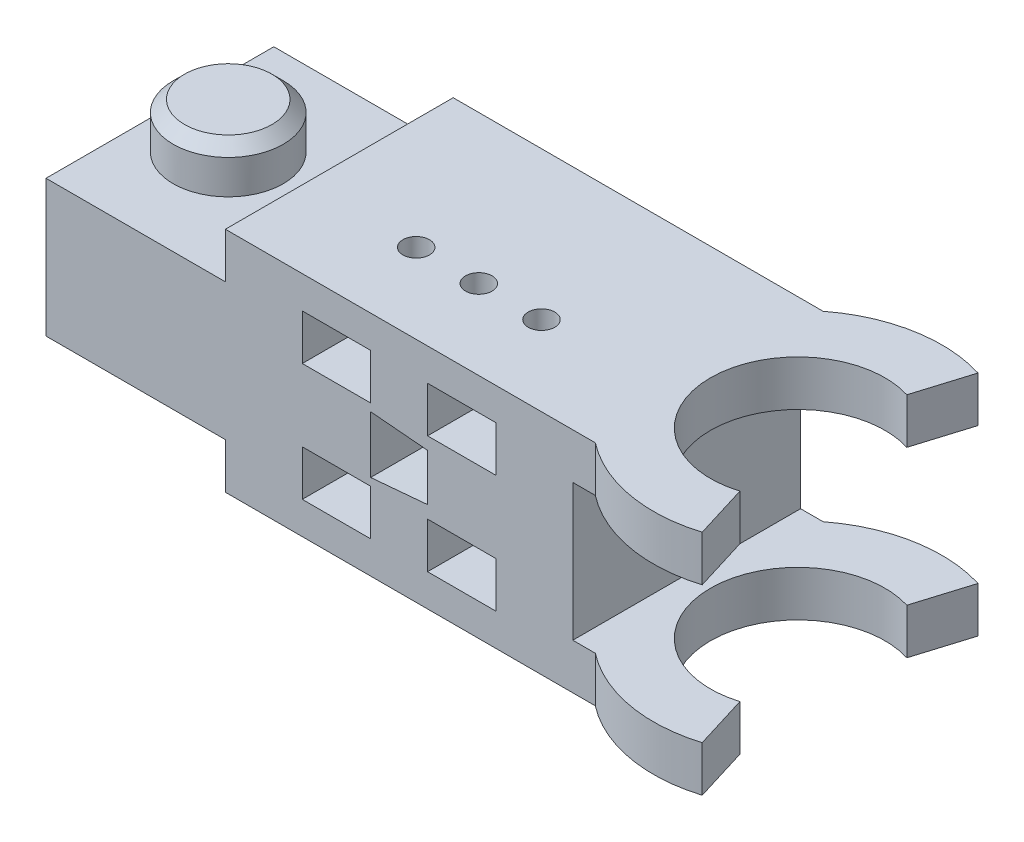
SolidWorks part; units mm, degrees
ref_plane "Front Plane" through (0, 0, 0) normal (0, 0, 1) x (1, 0, 0)
ref_plane "Top Plane" through (0, 0, 0) normal (0, 1, 0) x (1, 0, 0)
ref_plane "Right Plane" through (0, 0, 0) normal (1, 0, 0) x (0, 0, -1)
sketch "Sketch1" plane through (0, 0, 0) normal (0, 0, 1) x (1, 0, 0)
  line L0 (0, 0) -> (-19.5, 0) construction
  line L5 (-19.5, 0) -> (-30.5, 0) construction
  line L6 (-30.5, 0) -> (-50, 0) construction
  line L7 (-50, -6) -> (-42.5, -6) construction
  line L8 (-50, -10) -> (0, -10) construction
  line L9 (-50, -10) -> (-50, 10) construction
  line L10 (-50, 10) -> (0, 10) construction
  line L11 (0, -10) -> (0, 10) construction
  line L12 (-50, -10) -> (0, 10) construction
  line L13 (-50, 10) -> (0, -10) construction
  line L14 (-40.25, -10) -> (-40.25, -6)
  line L15 (-40.25, -6) -> (-50, -6)
  line L16 (-40.25, 10) -> (-40.25, 6)
  line L17 (-40.25, 6) -> (-50, 6)
  line L18 (-50, 6) -> (-56, 6)
  line L19 (-56, 6) -> (-56, -6)
  line L20 (-56, -6) -> (-50, -6)
  line L21 (-40.25, 10) -> (0, 10) construction
  line L22 (-40.25, -10) -> (0, -10)
  line L23 (0, 10) -> (2.25, 10)
  line L24 (2.25, 10) -> (2.25, 6)
  line L25 (2.25, 6) -> (0, 6)
  line L26 (0, -10) -> (2.25, -10)
  line L27 (2.25, -10) -> (2.25, -6)
  line L28 (2.25, -6) -> (0, -6)
  line L29 (0, 6) -> (0, -6) construction
  line L30 (0, 6) -> (-9.75, 6)
  line L31 (-9.75, 6) -> (-9.75, -6)
  line L32 (-9.75, -6) -> (0, -6)
  line L33 (-7.5, 0) -> (0, 0) construction
  line L34 (-7.5, 0) -> (-9.75, 0) construction
  line L35 (-40.25, 10) -> (0, 10)
  line L36 (0, 0) -> (2.25, 0) construction
  line L37 (2.25, 0) -> (2.25, 6) construction
  line L38 (-42.5, -6) -> (-40.25, -6) construction
  point P2 (-25, 0)
  dimension "D2" = 19.5
  dimension "D3" = 11
  dimension "D4" = 19.5
  dimension "D6" = 20
  dimension "D7" = 4
  dimension "D8" = 4
  dimension "D1" = 7.5
  dimension "D9" = 2.25
  dimension "D10" = 6
  dimension "D5" = 7.5
  dimension "D11" = 2.25
  dimension "D12" = 2.25
extrude "Boss-Extrude1" add sketch "Sketch1" along normal blind 20
sketch "Sketch2" plane through (0, -6, 0) normal (0, -1, 0) x (1, 0, 0)
  line L0 (-50, 0) -> (0, 0) construction
  line L1 (-50, 0) -> (0, 0) construction
  line L2 (-50, 0) -> (-50, 20) construction
  line L3 (-56, 20) -> (-40.25, 20) construction
  circle A0 centre (-50, 10) radius 4.835
  dimension "D1" = 9.67
extrude "Boss-Extrude2" add sketch "Sketch2" along normal blind 4
sketch "Sketch3" plane through (0, -10, 0) normal (0, -1, 0) x (1, 0, 0)
  line L0 (0, 0) -> (0, 20) construction
  line L1 (-40.25, 20) -> (2.25, 20) construction
  circle A0 centre (0, 10) radius 7.665
  dimension "D1" = 15.33
extrude "Cut-Extrude1" cut sketch "Sketch3" against normal up to surface (20 mm away) up to face at (-19, 10, 10)
mirror "Mirror1" about plane through (0, 0, 0) normal (0, 1, 0) of "Boss-Extrude2"
sketch "Sketch4" plane through (0, 0, 20) normal (0, 0, 1) x (1, 0, 0)
  line L0 (0, -10) -> (0, 10) construction
  line L1 (0, -10) -> (0, 10) construction
  line L2 (0, 0) -> (-25, 0) construction
  line L3 (-19.5, 0) -> (-30.5, 0) construction
  line L4 (-27.5, 2.5) -> (-22.5, 2.0626)
  line L5 (-27.5, -2.5) -> (-22.5, -2.5) construction
  line L6 (-27.5, -2.5) -> (-27.5, 2.5)
  line L7 (-27.5, 2.5) -> (-22.5, 2.5) construction
  line L8 (-22.5, -2.5) -> (-22.5, 2.5) construction
  line L9 (-27.5, -2.5) -> (-22.5, 2.5) construction
  line L10 (-27.5, 2.5) -> (-22.5, -2.5) construction
  line L11 (-27.5, -2.5) -> (-22.5, -2.0626)
  line L12 (-22.5, 2.0626) -> (-22.5, -2.0626)
  dimension "D1" = 5
  dimension "D2" = 5
  dimension "D3" = 25
  dimension "D4" = 5
  dimension "D5" = 5
extrude "Cut-Extrude2" cut sketch "Sketch4" against normal blind 10
sketch "Sketch5" plane through (0, 0, 20) normal (0, 0, 1) x (1, 0, 0)
  line L0 (-30.5, 0) -> (-50, 0) construction
  line L1 (-19.5, 0) -> (-30.5, 0) construction
  line L2 (0, 0) -> (-19.5, 0) construction
  line L3 (-30.5, 0) -> (-50, 0) construction
  line L4 (-19.5, 0) -> (-30.5, 0) construction
  line L5 (0, 0) -> (-19.5, 0) construction
  line L6 (-30.5, -5.165) -> (-30.5, 5.165) construction
  line L7 (-19.5, -5.165) -> (-19.5, 5.165) construction
  line L9 (-33.5, 7.165) -> (-27.5, 7.165)
  line L10 (-33.5, 7.165) -> (-33.5, 3.165)
  line L11 (-33.5, 3.165) -> (-27.5, 3.165)
  line L12 (-27.5, 7.165) -> (-27.5, 3.165)
  line L13 (-33.5, 7.165) -> (-27.5, 3.165) construction
  line L14 (-33.5, 3.165) -> (-27.5, 7.165) construction
  line L15 (-22.5, 7.165) -> (-16.5, 7.165)
  line L16 (-22.5, 7.165) -> (-22.5, 3.165)
  line L17 (-22.5, 3.165) -> (-16.5, 3.165)
  line L18 (-16.5, 7.165) -> (-16.5, 3.165)
  line L19 (-22.5, 7.165) -> (-16.5, 3.165) construction
  line L20 (-22.5, 3.165) -> (-16.5, 7.165) construction
  line L21 (-22.5, -7.165) -> (-16.5, -7.165)
  line L22 (-22.5, -7.165) -> (-22.5, -3.165)
  line L23 (-22.5, -3.165) -> (-16.5, -3.165)
  line L24 (-16.5, -7.165) -> (-16.5, -3.165)
  line L25 (-22.5, -7.165) -> (-16.5, -3.165) construction
  line L26 (-22.5, -3.165) -> (-16.5, -7.165) construction
  line L27 (-33.5, -7.165) -> (-27.5, -7.165)
  line L28 (-33.5, -7.165) -> (-33.5, -3.165)
  line L29 (-33.5, -3.165) -> (-27.5, -3.165)
  line L30 (-27.5, -7.165) -> (-27.5, -3.165)
  line L31 (-33.5, -7.165) -> (-27.5, -3.165) construction
  line L32 (-33.5, -3.165) -> (-27.5, -7.165) construction
  point P7 (-30.5, 0)
  point P10 (-19.5, 0)
  dimension "D2" = 6
  dimension "D3" = 6.33
extrude "Cut-Extrude3" cut sketch "Sketch5" against normal blind 10
sketch "Sketch6" plane through (0, -10, 0) normal (0, -1, 0) x (1, 0, 0)
  line L0 (-22.5, 10) -> (-16.5, 10) construction
  line L1 (-27.5, 10) -> (-22.5, 10) construction
  line L2 (-33.5, 10) -> (-27.5, 10) construction
  line L3 (-22.5, 10) -> (-16.5, 10) construction
  line L4 (-27.5, 10) -> (-22.5, 10) construction
  line L5 (-33.5, 10) -> (-27.5, 10) construction
  line L6 (-30.5, 10) -> (-30.5, 13) construction
  line L7 (-25, 10) -> (-25, 13) construction
  line L8 (-19.5, 10) -> (-19.5, 13) construction
  circle A0 centre (-30.5, 13) radius 1.165
  circle A1 centre (-25, 13) radius 1.165
  circle A2 centre (-19.5, 13) radius 1.165
  dimension "D2" = 2.33
  dimension "D1" = 3
extrude "Cut-Extrude4" cut sketch "Sketch6" against normal up to surface (20 mm away) up to face at (-13.5692, 10, 10)
sketch "Sketch10" plane through (0, -10, 0) normal (0, -1, 0) x (1, 0, 0)
  line L0 (2.25, 17.3273) -> (3.7177, 22.1071)
  line L1 (3.7177, -2.1071) -> (2.25, 2.6727)
  arc A0 (2.25, 17.3273) -> (2.25, 2.6727) centre (0, 10) ccw construction
  arc A1 (2.25, 17.3273) -> (2.25, 2.6727) centre (0, 10) ccw
  arc A2 (3.7177, 22.1071) -> (3.7177, -2.1071) centre (0, 10) ccw
  dimension "D1" = 5
extrude "Boss-Extrude4" add sketch "Sketch10" against normal up to surface (4 mm away) up to face at (-3.4025, -6, 10)
sketch "Sketch11" plane through (0, 10, 0) normal (0, 1, 0) x (1, 0, 0)
  line L5 (-9.75, -20) -> (-7.7719, -20)
  line L6 (3.7177, -22.1071) -> (2.25, -17.3273)
  line L8 (-7.7719, 0) -> (-9.75, 0)
  line L9 (-9.75, 0) -> (-9.75, -20)
  line L10 (-9.75, -20) -> (-7.7719, -20)
  line L13 (-7.7719, 0) -> (-9.75, 0)
  line L14 (-9.75, 0) -> (-9.75, -20)
  line L15 (3.7177, -22.1071) -> (2.25, -17.3273)
  line L17 (2.25, -2.6727) -> (3.7177, 2.1071)
  line L18 (2.25, -2.6727) -> (3.7177, 2.1071)
  arc A3 (-7.7719, -20) -> (3.7177, -22.1071) centre (0, -10) ccw
  arc A4 (2.25, -2.6727) -> (2.25, -17.3273) centre (0, -10) ccw
  arc A5 (-7.7719, -20) -> (3.7177, -22.1071) centre (0, -10) ccw
  arc A7 (2.25, -2.6727) -> (2.25, -17.3273) centre (0, -10) ccw
  arc A9 (3.7177, 2.1071) -> (-7.7719, 0) centre (0, -10) ccw
  arc A10 (3.7177, 2.1071) -> (-7.7719, 0) centre (0, -10) ccw
  dimension "D1" = 0
extrude "Boss-Extrude5" add sketch "Sketch11" against normal up to surface (4 mm away) up to face at (-3.4025, 6, 10)
chamfer "Chamfer1" distance 3 angle 45 3 edges at (-29.335, -10, 13) (-23.835, -10, 13) (-18.335, -10, 13)
chamfer "Chamfer2" distance 1 angle 45 1 edges at (-50, -10, 5.165)
chamfer "Chamfer3" distance 1 angle 45 1 edges at (-50, 10, 5.165)
sketch "Sketch14" plane through (0, 0, -2.75) normal (0, 0, -1) x (-1, 0, 0)
  line L12 (56, -3) -> (56, 3)
  line L13 (53, 6) -> (40.25, 6)
  line L14 (40.25, 6) -> (40.25, 7)
  line L15 (37.25, 10) -> (-3.7177, 10)
  line L16 (-3.7177, 10) -> (-3.7177, 6)
  line L17 (-3.7177, 6) -> (9.75, 6)
  line L18 (9.75, 6) -> (9.75, -6)
  line L19 (9.75, -6) -> (-3.7177, -6)
  line L20 (-3.7177, -6) -> (-3.7177, -10)
  line L21 (-3.7177, -10) -> (37.25, -10)
  line L22 (40.25, -7) -> (40.25, -6)
  line L23 (40.25, -6) -> (53, -6)
  line L24 (56, -3) -> (56, 3)
  line L25 (53, 6) -> (40.25, 6)
  line L26 (40.25, 6) -> (40.25, 7)
  line L27 (37.25, 10) -> (-3.7177, 10)
  line L28 (-3.7177, 10) -> (-3.7177, 6)
  line L29 (-3.7177, 6) -> (9.75, 6)
  line L30 (9.75, 6) -> (9.75, -6)
  line L31 (9.75, -6) -> (-3.7177, -6)
  line L32 (-3.7177, -6) -> (-3.7177, -10)
  line L33 (-3.7177, -10) -> (37.25, -10)
  line L34 (40.25, -7) -> (40.25, -6)
  line L35 (40.25, -6) -> (53, -6)
  arc A4 (53, -6) -> (56, -3) centre (53, -3) ccw
  arc A5 (56, 3) -> (53, 6) centre (53, 3) ccw
  arc A6 (40.25, 7) -> (37.25, 10) centre (37.25, 7) ccw
  arc A7 (37.25, -10) -> (40.25, -7) centre (37.25, -7) ccw
  arc A8 (53, -6) -> (56, -3) centre (53, -3) ccw
  arc A9 (56, 3) -> (53, 6) centre (53, 3) ccw
  arc A10 (40.25, 7) -> (37.25, 10) centre (37.25, 7) ccw
  arc A11 (37.25, -10) -> (40.25, -7) centre (37.25, -7) ccw
  dimension "D1" = 0
equation "\"offset\"=5"
equation "\"x_0\"= 19.5"
equation "\"D2@Sketch1\"=\"x_0\""
equation "\"x_1\"= 11"
equation "\"D3@Sketch1\"=\"x_1\""
equation "\"x_2\"= 19.5"
equation "\"D4@Sketch1\"=\"x_2\""
equation "\"bearing_width\"= 4"
equation "\"link_width\"= 20"
equation "\"link_height\"= 20"
equation "\"D6@Sketch1\"=\"link_width\""
equation "\"D7@Sketch1\"=\"bearing_width\""
equation "\"D8@Sketch1\"=\"bearing_width\""
equation "\"D1@Boss-Extrude1\"=\"link_height\""
equation "\"D1@Boss-Extrude2\"=\"bearing_width\""
equation "\"bearing_OD\"=15"
equation "\"bearing_ID\"=10"
equation "\"D1@Sketch3\"=\"bearing_OD\"+\"tol\""
equation "\"D1@Sketch1\"=\"bearing_OD\"/2"
equation "\"bearing_offset\"= 2.25"
equation "\"D9@Sketch1\"=\"bearing_offset\""
equation "\"bearing_backstop_offset\"=6"
equation "\"D10@Sketch1\"=\"bearing_backstop_offset\""
equation "\"D5@Sketch1\"=\"bearing_OD\"/2"
equation "\"D11@Sketch1\"=\"bearing_offset\""
equation "\"D12@Sketch1\"=\"bearing_offset\""
equation "\"chuck_width\"=5"
equation "\"D4@Sketch4\"=\"chuck_width\""
equation "\"chuck_angle\"=5"
equation "\"D2@Sketch4\"=\"chuck_angle\""
equation "\"D1@Sketch4\"=\"chuck_angle\""
equation "\"chuck_length\"=5"
equation "\"chuck_depth\"= 10"
equation "\"D1@Cut-Extrude2\"=\"chuck_depth\""
equation "\"D5@Sketch4\"=\"chuck_length\""
equation "\"chuck_distance\"=25"
equation "\"D3@Sketch4\"=\"chuck_distance\""
equation "\"post_width\"=4"
equation "\"D1@Sketch5\"=\"post_width\""
equation "\"post_length\"=6"
equation "\"D2@Sketch5\"=\"post_length\""
equation "\"post_bearing_width\"=6"
equation "\"D3@Sketch5\"=\"post_bearing_width\"+\"tol\""
equation "\"post_depth\"=10"
equation "\"D1@Cut-Extrude3\"=\"post_depth\""
equation "\"pin_offset\"= 3"
equation "\"D1@Sketch6\"=\"pin_offset\""
equation "\"pin_dia\"=2"
equation "\"D2@Sketch6\"=\"pin_dia\"+\"tol\""
equation "\"D1@Sketch2\"=\"bearing_ID\"-\"tol\""
equation "\"tol\"= 0.33"
equation "\"D1@Sketch8\"=4.00mm+\"tol\""
equation "\"D1@Sketch12\"=\"tol\"/2"
